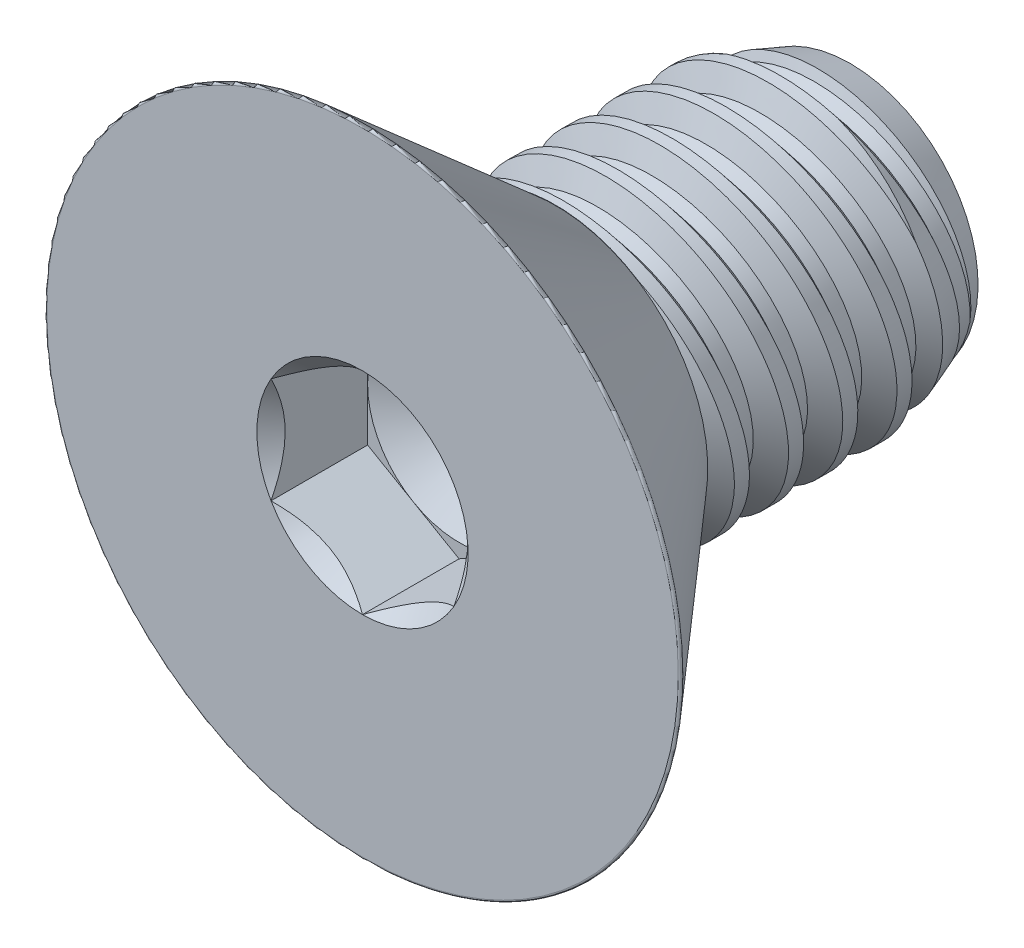
SolidWorks part; units mm, degrees
ref_plane "Front" through (0, 0, 0) normal (0, 0, 1) x (1, 0, 0)
ref_plane "Top" through (0, 0, 0) normal (0, 1, 0) x (1, 0, 0)
ref_plane "Right" through (0, 0, 0) normal (1, 0, 0) x (0, 0, -1)
sketch "Sketch1" plane through (0, 0, 0) normal (1, 0, 0) x (0, 0, -1)
  line L0 (0, 0) -> (-5.0292, 0) construction
  line L1 (0, 0) -> (7.6708, 0)
  line L2 (0, 0) -> (0, 3.9688)
  line L3 (0, 3.9688) -> (7.6708, 3.9688)
  line L4 (7.6708, 0) -> (7.6708, 3.9688)
  line L5 (0, -3.9688) -> (7.6708, -3.9687) construction
  dimension "D1" = 7.6708
  dimension "Thread Dia" = 7.9375
  dimension "Length" = 12.7
  dimension "Head Height" = 5.0292
revolve "Revolve1" add sketch "Sketch1" angle 360 about L0
ref_plane "Plane1" through (0, 0, 5.0292) normal (0, 0, 1) x (1, 0, 0)
sketch "Sketch2" plane through (0, 0, 0) normal (1, 0, 0) x (0, 0, -1)
  line L0 (0, 3.9688) -> (0, -3.9688) construction
  line L1 (0, -3.9688) -> (1.4111, -3.9688) construction
  line L2 (1.4111, -3.9688) -> (0, 3.9688) construction
  line L3 (0, 3.9688) -> (0.1737, 3.9996) construction
  line L4 (0.1737, 3.9996) -> (1.3893, 4.2157)
  line L5 (1.3893, 4.2157) -> (1.0889, 3.3866)
  line L6 (1.0889, 3.3866) -> (0.7415, 3.3248)
  line L7 (0.7415, 3.3248) -> (0.1737, 3.9996)
  line L8 (0.9152, 3.3557) -> (0.7815, 4.1077) construction
  line L9 (0, -3.9688) -> (7.6708, -3.9688) construction
  line L10 (0, 3.9688) -> (7.6708, 3.9688) construction
  line L12 (0.8062, 3.9688) -> (2.2173, -3.9688) construction
  line L13 (0, -0.2688) -> (3.0235, 0.2688) construction
  line L15 (0, 0) -> (0, 3.9688) construction
  point P19 (1.5118, 0)
  dimension "D1" = 60
  dimension "Thread Pitch" = 1.4111
  dimension "D2" = 0.1764
  dimension "D3" = 0.3528
  dimension "D4" = 1.4111
revolve "Cut-Revolve1" cut sketch "Sketch2" angle 360 about L13
sketch "Sketch3" plane through (0, 0, 0) normal (1, 0, 0) x (0, 0, -1)
  line L0 (7.6708, 3.3248) -> (5.9016, 3.9688)
  line L1 (5.9016, 3.9688) -> (7.6708, 3.9688)
  line L2 (7.6708, 3.9688) -> (7.6708, 3.3248)
  line L3 (0, 3.9688) -> (7.6708, 3.9688) construction
  line L4 (7.6708, 0) -> (7.6708, 3.9688) construction
  line L5 (5.9016, 0) -> (0, 0) construction
  line L6 (5.9016, 3.9688) -> (5.9016, -3.9688) construction
  line L7 (0, -3.9688) -> (7.6708, -3.9688) construction
  dimension "D1" = 20
  dimension "D2" = 7.9375
revolve "Cut-Revolve2" cut sketch "Sketch3" angle 360 about L5
pattern_linear "LPattern1" count 5 spacing 1.4111 along (0, 0, -1) of "Cut-Revolve1"
pattern_linear "LPattern2" count 2 spacing 1.4111 along (0, 0, 1) of "Cut-Revolve1"
sketch "Sketch4" plane through (0, 0, 0) normal (0, 0, 1) x (1, 0, 0)
  circle A0 centre (0, 0) radius 8.3312
  dimension "Head Dia" = 16.6624
extrude "Extrude1" add sketch "Sketch4" along normal up to surface (5.0292 mm away) up to plane "Plane1"
sketch "Sketch9" plane through (0, 0, 0) normal (1, 0, 0) x (0, 0, -1)
  line L0 (-5.0292, 8.3312) -> (0, 3.9594)
  line L1 (0, 3.9594) -> (0, 8.3312)
  line L2 (0, 8.3312) -> (-5.0292, 8.3312)
  line L3 (0, 0) -> (-5.0292, 0) construction
  line L6 (-5.0292, -8.3312) -> (0, -3.9594) construction
  line L7 (0, -8.3312) -> (0, 8.3312) construction
  line L8 (-5.0292, 8.3312) -> (-5.0292, -8.3312) construction
  line L9 (0, 8.3312) -> (-5.0292, 8.3312) construction
  dimension "D1" = 82
revolve "Cut-Revolve3" cut sketch "Sketch9" angle 360 about L3
fillet "Fillet1" radius 0.0508 1 edges at (0, 8.3312, 5.0292)
sketch "Sketch6" plane through (0, 0, 5.0292) normal (0, 0, 1) x (1, 0, 0)
  line L1 (0, -2.7496) -> (2.3812, -1.3748)
  line L2 (2.3812, -1.3748) -> (2.3812, 1.3748)
  line L3 (2.3812, 1.3748) -> (0, 2.7496)
  line L4 (0, 2.7496) -> (-2.3812, 1.3748)
  line L5 (-2.3812, 1.3748) -> (-2.3812, -1.3748)
  line L6 (-2.3812, -1.3748) -> (0, -2.7496)
  circle A0 centre (0, 0) radius 2.3812 construction
  dimension "Hex" = 4.7625
extrude "Cut-Extrude1" cut sketch "Sketch6" against normal blind 2.5146
sketch "Sketch7" plane through (0, 0, 5.0292) normal (0, 0, 1) x (1, 0, 0)
  circle A0 centre (0, 0) radius 2.7496
extrude "Cut-Extrude4" cut sketch "Sketch7" against normal blind 2.5146 draft 45
sketch "Sketch8" plane through (0, 0, 2.5146) normal (0, 0, 1) x (1, 0, 0)
  circle A0 centre (0, 0) radius 2.3812 construction
  circle A1 centre (0, 0) radius 2.3812
extrude "Cut-Extrude5" cut sketch "Sketch8" against normal blind 0.8382 draft 60
equation "\"D2@Sketch2\"=\"Thread Pitch@Sketch2\"/8"
equation "\"D3@Sketch2\"=\"Thread Pitch@Sketch2\"/4"
equation "\"D4@Sketch2\"=\"Thread Pitch@Sketch2\""
equation "\"D3@LPattern1\"=\"Thread Pitch@Sketch2\""
equation "\"D1@Cut-Extrude1\"=\"Head Height@Sketch1\"/2"
equation "\"D1@Cut-Extrude4\"=\"D1@Cut-Extrude1\""
equation "\"D1@Cut-Extrude5\"=\"D1@Cut-Extrude1\"/3"
equation "\"D1@LPattern1\"=\"D1@Sketch1\"/\"Thread Pitch@Sketch2\""
equation "\"D3@LPattern2\"=\"Thread Pitch@Sketch2\""
